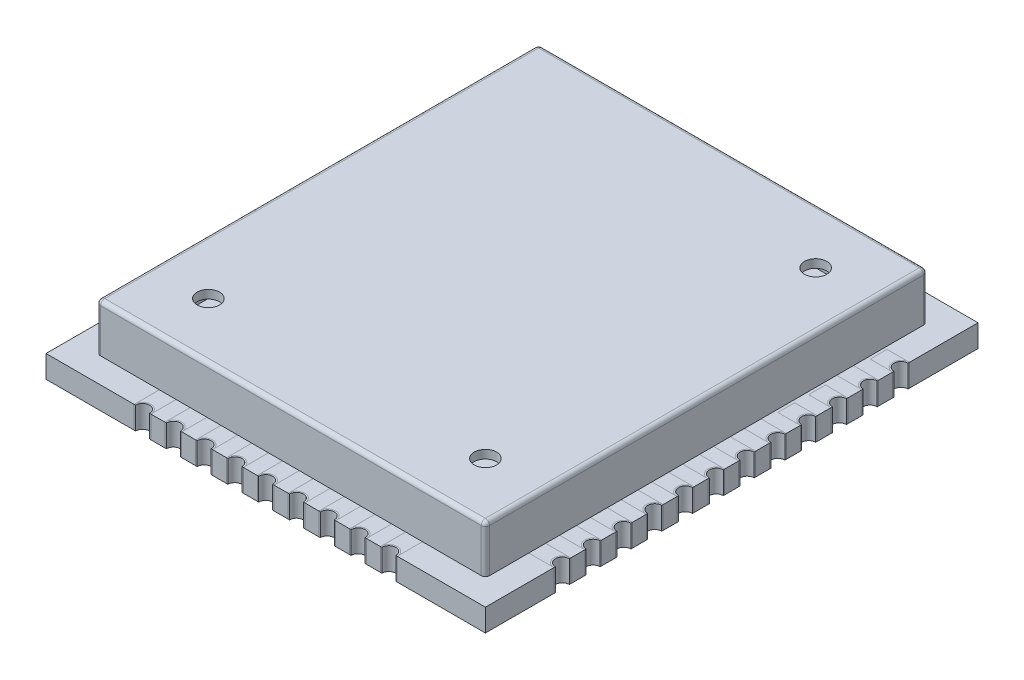
SolidWorks part; units mm, degrees
note: The reader was unsure of these and kept them because the rebuilt part matched: shared geometry of "Sketch5<2>", "Sketch5<3>", "Sketch5<4>", "Sketch3<2>".
other "Shield"
other "PCB"
ref_plane "Front Plane" through (0, 0, 0) normal (0, 0, 1) x (1, 0, 0)
ref_plane "Top Plane" through (0, 0, 0) normal (0, 1, 0) x (1, 0, 0)
ref_plane "Right Plane" through (0, 0, 0) normal (1, 0, 0) x (0, 0, -1)
sketch "Sketch1" plane through (0, 0, 0) normal (0, 1, 0) x (1, 0, 0)
  line L1 (-7.85, -8.8) -> (7.85, -8.8)
  line L2 (-7.85, -8.8) -> (-7.85, 8.8)
  line L3 (-7.85, 8.8) -> (7.85, 8.8)
  line L4 (7.85, -8.8) -> (7.85, 8.8)
  line L5 (-7.85, -8.8) -> (7.85, 8.8) construction
  line L6 (-7.85, 8.8) -> (7.85, -8.8) construction
  point P0 (0, 0)
  dimension "D1" = 17.6
  dimension "D2" = 15.7
extrude "PCB BASE" add sketch "Sketch1" along normal blind 0.8
sketch "Sketch2" plane through (0, 0, 0) normal (0, 1, 0) x (1, 0, 0)
  line L1 (-6.95, -7.9) -> (6.95, -7.9)
  line L2 (-6.95, -7.9) -> (-6.95, 7.9)
  line L3 (-6.95, 7.9) -> (6.95, 7.9)
  line L4 (6.95, -7.9) -> (6.95, 7.9)
  line L5 (-6.95, -7.9) -> (6.95, 7.9) construction
  line L6 (-6.95, 7.9) -> (6.95, -7.9) construction
  point P0 (0, 0)
  dimension "D1" = 15.8
  dimension "D2" = 13.9
extrude "SHIELD" add sketch "Sketch2" along normal blind 1.7 from surface at 0.8 separate body starting at face at (0, 0.8, 0)
shell "Shield shelling" thickness 0.3
sketch "Sketch4" plane through (0, 0, 0) normal (0, 1, 0) x (1, 0, 0)
  line L0 (-6.95, 7.9) -> (-6.95, -7.9) construction
  line L1 (-6.95, -7.9) -> (6.95, -7.9) construction
  line L2 (6.95, -7.9) -> (6.95, 7.9) construction
  line L3 (6.95, 7.9) -> (-6.95, 7.9) construction
  circle A0 centre (-4.95, -5.9) radius 0.4
  circle A1 centre (4.95, 5.9) radius 0.4
  circle A2 centre (4.95, -5.9) radius 0.4
  dimension "D1" = 0.8
  dimension "D2" = 0.8
  dimension "D3" = 0.8
  dimension "D4" = 2
  dimension "D5" = 2
  dimension "D6" = 2
  dimension "D7" = 2
extrude "Holes in shield" cut sketch "Sketch4" against normal up to next from surface
sketch "Sketch3" plane through (0, 0, 0) normal (0, 1, 0) x (1, 0, 0)
  line L0 (-7.85, 8.8) -> (-7.85, -8.8) construction
  line L1 (-7.85, -8.8) -> (7.85, -8.8) construction
  line L2 (-7.85, -5.75) -> (-7.85, -6.35)
  line L3 (-7.85, -4.65) -> (-7.85, -5.25)
  line L4 (-7.85, -3.55) -> (-7.85, -4.15)
  line L5 (-7.85, -2.45) -> (-7.85, -3.05)
  line L6 (-7.85, -1.35) -> (-7.85, -1.95)
  line L7 (-7.85, -0.25) -> (-7.85, -0.85)
  line L8 (-7.85, 0.85) -> (-7.85, 0.25)
  line L9 (-7.85, 1.95) -> (-7.85, 1.35)
  line L10 (-7.85, 3.05) -> (-7.85, 2.45)
  line L11 (-7.85, 4.15) -> (-7.85, 3.55)
  line L12 (-7.85, 5.25) -> (-7.85, 4.65)
  line L13 (-7.85, 6.35) -> (-7.85, 5.75)
  line L14 (0, 8.8) -> (0, -8.8) construction
  line L15 (7.85, 8.8) -> (-7.85, 8.8) construction
  line L16 (7.85, 6.35) -> (7.85, 5.75)
  line L17 (7.85, 5.25) -> (7.85, 4.65)
  line L18 (7.85, 4.15) -> (7.85, 3.55)
  line L19 (7.85, 3.05) -> (7.85, 2.45)
  line L20 (7.85, 1.95) -> (7.85, 1.35)
  line L21 (7.85, 0.85) -> (7.85, 0.25)
  line L22 (7.85, -0.25) -> (7.85, -0.85)
  line L23 (7.85, -1.35) -> (7.85, -1.95)
  line L24 (7.85, -2.45) -> (7.85, -3.05)
  line L25 (7.85, -3.55) -> (7.85, -4.15)
  line L26 (7.85, -4.65) -> (7.85, -5.25)
  line L27 (7.85, -5.75) -> (7.85, -6.35)
  line L28 (-4.7, -8.8) -> (-4.1, -8.8)
  line L29 (-3.6, -8.8) -> (-3, -8.8)
  line L30 (-2.5, -8.8) -> (-1.9, -8.8)
  line L31 (-1.4, -8.8) -> (-0.8, -8.8)
  line L32 (-0.3, -8.8) -> (0.3, -8.8)
  line L33 (0.8, -8.8) -> (1.4, -8.8)
  line L34 (1.9, -8.8) -> (2.5, -8.8)
  line L35 (3, -8.8) -> (3.6, -8.8)
  line L36 (4.1, -8.8) -> (4.7, -8.8)
  line L37 (-7.85, 0) -> (7.85, 0) construction
  line L38 (7.85, -8.8) -> (7.85, 8.8) construction
  line L39 (4.1, 8.8) -> (4.7, 8.8)
  line L40 (3, 8.8) -> (3.6, 8.8)
  line L41 (1.9, 8.8) -> (2.5, 8.8)
  line L42 (0.8, 8.8) -> (1.4, 8.8)
  line L43 (-0.3, 8.8) -> (0.3, 8.8)
  line L44 (-1.4, 8.8) -> (-0.8, 8.8)
  line L45 (-2.5, 8.8) -> (-1.9, 8.8)
  line L46 (-3.6, 8.8) -> (-3, 8.8)
  line L47 (-4.7, 8.8) -> (-4.1, 8.8)
  arc A0 (-7.85, -5.75) -> (-7.85, -6.35) centre (-7.85, -6.05) cw
  arc A1 (-7.85, -4.65) -> (-7.85, -5.25) centre (-7.85, -4.95) cw
  arc A2 (-7.85, -3.55) -> (-7.85, -4.15) centre (-7.85, -3.85) cw
  arc A3 (-7.85, -2.45) -> (-7.85, -3.05) centre (-7.85, -2.75) cw
  arc A4 (-7.85, -1.35) -> (-7.85, -1.95) centre (-7.85, -1.65) cw
  arc A5 (-7.85, -0.25) -> (-7.85, -0.85) centre (-7.85, -0.55) cw
  arc A6 (-7.85, 0.85) -> (-7.85, 0.25) centre (-7.85, 0.55) cw
  arc A7 (-7.85, 1.95) -> (-7.85, 1.35) centre (-7.85, 1.65) cw
  arc A8 (-7.85, 3.05) -> (-7.85, 2.45) centre (-7.85, 2.75) cw
  arc A9 (-7.85, 4.15) -> (-7.85, 3.55) centre (-7.85, 3.85) cw
  arc A10 (-7.85, 5.25) -> (-7.85, 4.65) centre (-7.85, 4.95) cw
  arc A11 (-7.85, 6.35) -> (-7.85, 5.75) centre (-7.85, 6.05) cw
  arc A12 (7.85, 6.35) -> (7.85, 5.75) centre (7.85, 6.05) ccw
  arc A13 (7.85, 5.25) -> (7.85, 4.65) centre (7.85, 4.95) ccw
  arc A14 (7.85, 4.15) -> (7.85, 3.55) centre (7.85, 3.85) ccw
  arc A15 (7.85, 3.05) -> (7.85, 2.45) centre (7.85, 2.75) ccw
  arc A16 (7.85, 1.95) -> (7.85, 1.35) centre (7.85, 1.65) ccw
  arc A17 (7.85, 0.85) -> (7.85, 0.25) centre (7.85, 0.55) ccw
  arc A18 (7.85, -0.25) -> (7.85, -0.85) centre (7.85, -0.55) ccw
  arc A19 (7.85, -1.35) -> (7.85, -1.95) centre (7.85, -1.65) ccw
  arc A20 (7.85, -2.45) -> (7.85, -3.05) centre (7.85, -2.75) ccw
  arc A21 (7.85, -3.55) -> (7.85, -4.15) centre (7.85, -3.85) ccw
  arc A22 (7.85, -4.65) -> (7.85, -5.25) centre (7.85, -4.95) ccw
  arc A23 (7.85, -5.75) -> (7.85, -6.35) centre (7.85, -6.05) ccw
  arc A24 (-4.7, -8.8) -> (-4.1, -8.8) centre (-4.4, -8.8) cw
  arc A25 (-3.6, -8.8) -> (-3, -8.8) centre (-3.3, -8.8) cw
  arc A26 (-2.5, -8.8) -> (-1.9, -8.8) centre (-2.2, -8.8) cw
  arc A27 (-1.4, -8.8) -> (-0.8, -8.8) centre (-1.1, -8.8) cw
  arc A28 (-0.3, -8.8) -> (0.3, -8.8) centre (0, -8.8) cw
  arc A29 (0.8, -8.8) -> (1.4, -8.8) centre (1.1, -8.8) cw
  arc A30 (1.9, -8.8) -> (2.5, -8.8) centre (2.2, -8.8) cw
  arc A31 (3, -8.8) -> (3.6, -8.8) centre (3.3, -8.8) cw
  arc A32 (4.1, -8.8) -> (4.7, -8.8) centre (4.4, -8.8) cw
  arc A33 (4.1, 8.8) -> (4.7, 8.8) centre (4.4, 8.8) ccw
  arc A34 (3, 8.8) -> (3.6, 8.8) centre (3.3, 8.8) ccw
  arc A35 (1.9, 8.8) -> (2.5, 8.8) centre (2.2, 8.8) ccw
  arc A36 (0.8, 8.8) -> (1.4, 8.8) centre (1.1, 8.8) ccw
  arc A37 (-0.3, 8.8) -> (0.3, 8.8) centre (0, 8.8) ccw
  arc A38 (-1.4, 8.8) -> (-0.8, 8.8) centre (-1.1, 8.8) ccw
  arc A39 (-2.5, 8.8) -> (-1.9, 8.8) centre (-2.2, 8.8) ccw
  arc A40 (-3.6, 8.8) -> (-3, 8.8) centre (-3.3, 8.8) ccw
  arc A41 (-4.7, 8.8) -> (-4.1, 8.8) centre (-4.4, 8.8) ccw
  point P0 (-7.85, -6.05)
  dimension "D2" = 0.3
  dimension "D4" = 0.3
  dimension "D1" = 2.75
  dimension "D5" = 3.45
  dimension "D3" = 12
  dimension "D6" = 9
extrude "Cut-Extrude1" cut sketch "Sketch3" against normal through all and the other way through all
sketch "Sketch5" plane through (0, 0, 0) normal (0, 1, 0) x (1, 0, 0)
  line L0 (-7.85, -4.65) -> (-6.85, -4.65)
  line L1 (-7.85, -5.75) -> (-6.85, -5.75)
  line L2 (-7.85, -5.75) -> (-7.85, -6.35)
  line L3 (-7.85, -6.35) -> (-6.85, -6.35)
  line L4 (-6.85, -5.75) -> (-6.85, -6.35)
  line L5 (-7.85, -4.65) -> (-7.85, -5.25)
  line L6 (-7.85, -5.25) -> (-6.85, -5.25)
  line L7 (-6.85, -4.65) -> (-6.85, -5.25)
  line L8 (-7.85, -3.55) -> (-6.85, -3.55)
  line L9 (-7.85, -3.55) -> (-7.85, -4.15)
  line L10 (-7.85, -4.15) -> (-6.85, -4.15)
  line L11 (-6.85, -3.55) -> (-6.85, -4.15)
  line L12 (-7.85, -2.45) -> (-6.85, -2.45)
  line L13 (-7.85, -2.45) -> (-7.85, -3.05)
  line L14 (-7.85, -3.05) -> (-6.85, -3.05)
  line L15 (-6.85, -2.45) -> (-6.85, -3.05)
  line L16 (-7.85, -1.35) -> (-6.85, -1.35)
  line L17 (-7.85, -1.35) -> (-7.85, -1.95)
  line L18 (-7.85, -1.95) -> (-6.85, -1.95)
  line L19 (-6.85, -1.35) -> (-6.85, -1.95)
  line L20 (-7.85, -0.25) -> (-6.85, -0.25)
  line L21 (-7.85, -0.25) -> (-7.85, -0.85)
  line L22 (-7.85, -0.85) -> (-6.85, -0.85)
  line L23 (-6.85, -0.25) -> (-6.85, -0.85)
  line L24 (-7.85, 0.85) -> (-6.85, 0.85)
  line L25 (-7.85, 0.85) -> (-7.85, 0.25)
  line L26 (-7.85, 0.25) -> (-6.85, 0.25)
  line L27 (-6.85, 0.85) -> (-6.85, 0.25)
  line L28 (-7.85, 1.95) -> (-6.85, 1.95)
  line L29 (-7.85, 1.95) -> (-7.85, 1.35)
  line L30 (-7.85, 1.35) -> (-6.85, 1.35)
  line L31 (-6.85, 1.95) -> (-6.85, 1.35)
  line L32 (-7.85, 3.05) -> (-6.85, 3.05)
  line L33 (-7.85, 3.05) -> (-7.85, 2.45)
  line L34 (-7.85, 2.45) -> (-6.85, 2.45)
  line L35 (-6.85, 3.05) -> (-6.85, 2.45)
  line L36 (-7.85, 4.15) -> (-6.85, 4.15)
  line L37 (-7.85, 4.15) -> (-7.85, 3.55)
  line L38 (-7.85, 3.55) -> (-6.85, 3.55)
  line L39 (-6.85, 4.15) -> (-6.85, 3.55)
  line L40 (-7.85, 5.25) -> (-6.85, 5.25)
  line L41 (-7.85, 5.25) -> (-7.85, 4.65)
  line L42 (-7.85, 4.65) -> (-6.85, 4.65)
  line L43 (-6.85, 5.25) -> (-6.85, 4.65)
  line L44 (-7.85, 6.35) -> (-6.85, 6.35)
  line L45 (-7.85, 6.35) -> (-7.85, 5.75)
  line L46 (-7.85, 5.75) -> (-6.85, 5.75)
  line L47 (-6.85, 6.35) -> (-6.85, 5.75)
  line L48 (-7.85, 0) -> (7.85, 0) construction
  line L49 (-7.85, 0.25) -> (-7.85, -0.25) construction
  line L50 (7.85, -0.25) -> (7.85, 0.25) construction
  line L51 (0, 8.5) -> (0, -8.5) construction
  line L52 (7.85, 5.25) -> (7.05, 5.25) [skipped]
  line L53 (7.85, 6.35) -> (7.05, 6.35)
  line L54 (7.85, 6.35) -> (7.85, 5.75)
  line L55 (7.85, 5.75) -> (7.05, 5.75)
  line L56 (7.05, 6.35) -> (7.05, 5.75)
  line L57 (7.85, 5.25) -> (7.85, 4.65) [skipped]
  line L58 (7.85, 4.65) -> (7.05, 4.65) [skipped]
  line L59 (7.05, 5.25) -> (7.05, 4.65) [skipped]
  line L60 (7.85, 4.15) -> (7.05, 4.15)
  line L61 (7.85, 4.15) -> (7.85, 3.55)
  line L62 (7.85, 3.55) -> (7.05, 3.55)
  line L63 (7.05, 4.15) -> (7.05, 3.55)
  line L64 (7.85, 3.05) -> (7.05, 3.05)
  line L65 (7.85, 3.05) -> (7.85, 2.45)
  line L66 (7.85, 2.45) -> (7.05, 2.45)
  line L67 (7.05, 3.05) -> (7.05, 2.45)
  line L68 (6.85, 1.95) -> (6.85, 1.35)
  line L69 (7.85, 1.35) -> (6.85, 1.35)
  line L70 (7.85, 1.95) -> (7.85, 1.35)
  line L71 (7.85, 1.95) -> (6.85, 1.95)
  line L72 (6.85, 0.85) -> (6.85, 0.25)
  line L73 (7.85, 0.25) -> (6.85, 0.25)
  line L74 (7.85, 0.85) -> (7.85, 0.25)
  line L75 (7.85, 0.85) -> (6.85, 0.85)
  line L76 (6.85, -0.25) -> (6.85, -0.85)
  line L77 (7.85, -0.85) -> (6.85, -0.85)
  line L78 (7.85, -0.25) -> (7.85, -0.85)
  line L79 (7.85, -0.25) -> (6.85, -0.25)
  line L80 (6.85, -1.35) -> (6.85, -1.95)
  line L81 (7.85, -1.95) -> (6.85, -1.95)
  line L82 (7.85, -1.35) -> (7.85, -1.95)
  line L83 (7.85, -1.35) -> (6.85, -1.35)
  line L84 (6.85, -2.45) -> (6.85, -3.05)
  line L85 (7.85, -3.05) -> (6.85, -3.05)
  line L86 (7.85, -2.45) -> (7.85, -3.05)
  line L87 (7.85, -2.45) -> (6.85, -2.45)
  line L88 (6.85, -3.55) -> (6.85, -4.15)
  line L89 (7.85, -4.15) -> (6.85, -4.15)
  line L90 (7.85, -3.55) -> (7.85, -4.15)
  line L91 (7.85, -3.55) -> (6.85, -3.55)
  line L92 (6.85, -4.65) -> (6.85, -5.25)
  line L93 (7.85, -5.25) -> (6.85, -5.25)
  line L94 (7.85, -4.65) -> (7.85, -5.25)
  line L95 (6.85, -5.75) -> (6.85, -6.35)
  line L96 (7.85, -6.35) -> (6.85, -6.35)
  line L97 (7.85, -5.75) -> (7.85, -6.35)
  line L98 (7.85, -5.75) -> (6.85, -5.75)
  line L99 (7.85, -4.65) -> (6.85, -4.65)
  line L100 (-3.6, -8.8) -> (-3, -8.8)
  line L101 (-4.7, -8.8) -> (-4.1, -8.8)
  line L102 (-4.7, -8.8) -> (-4.7, -7.8)
  line L103 (-4.7, -7.8) -> (-4.1, -7.8)
  line L104 (-4.1, -8.8) -> (-4.1, -7.8)
  line L105 (-3.6, -8.8) -> (-3.6, -7.8)
  line L106 (-3.6, -7.8) -> (-3, -7.8)
  line L107 (-3, -8.8) -> (-3, -7.8)
  line L108 (-2.5, -8.8) -> (-1.9, -8.8)
  line L109 (-2.5, -8.8) -> (-2.5, -7.8)
  line L110 (-2.5, -7.8) -> (-1.9, -7.8)
  line L111 (-1.9, -8.8) -> (-1.9, -7.8)
  line L112 (-1.4, -8.8) -> (-0.8, -8.8)
  line L113 (-1.4, -8.8) -> (-1.4, -7.8)
  line L114 (-1.4, -7.8) -> (-0.8, -7.8)
  line L115 (-0.8, -8.8) -> (-0.8, -7.8)
  line L116 (-0.3, -8.8) -> (0.3, -8.8)
  line L117 (-0.3, -8.8) -> (-0.3, -7.8)
  line L118 (-0.3, -7.8) -> (0.3, -7.8)
  line L119 (0.3, -8.8) -> (0.3, -7.8)
  line L120 (0.8, -8.8) -> (1.4, -8.8)
  line L121 (0.8, -8.8) -> (0.8, -7.8)
  line L122 (0.8, -7.8) -> (1.4, -7.8)
  line L123 (1.4, -8.8) -> (1.4, -7.8)
  line L124 (1.9, -8.8) -> (2.5, -8.8)
  line L125 (1.9, -8.8) -> (1.9, -7.8)
  line L126 (1.9, -7.8) -> (2.5, -7.8)
  line L127 (2.5, -8.8) -> (2.5, -7.8)
  line L128 (3, -8.8) -> (3.6, -8.8)
  line L129 (3, -8.8) -> (3, -7.8)
  line L130 (3, -7.8) -> (3.6, -7.8)
  line L131 (3.6, -8.8) -> (3.6, -7.8)
  line L132 (4.1, -8.8) -> (4.7, -8.8)
  line L133 (4.1, -8.8) -> (4.1, -7.8)
  line L134 (4.1, -7.8) -> (4.7, -7.8)
  line L135 (4.7, -8.8) -> (4.7, -7.8)
  line L136 (4.7, 8.8) -> (4.7, 7.8)
  line L137 (4.1, 7.8) -> (4.7, 7.8)
  line L138 (4.1, 8.8) -> (4.1, 7.8)
  line L139 (4.1, 8.8) -> (4.7, 8.8)
  line L140 (3.6, 8.8) -> (3.6, 7.8)
  line L141 (3, 7.8) -> (3.6, 7.8)
  line L142 (3, 8.8) -> (3, 7.8)
  line L143 (3, 8.8) -> (3.6, 8.8)
  line L144 (2.5, 8.8) -> (2.5, 7.8)
  line L145 (1.9, 7.8) -> (2.5, 7.8)
  line L146 (1.9, 8.8) -> (1.9, 7.8)
  line L147 (1.9, 8.8) -> (2.5, 8.8)
  line L148 (1.4, 8.8) -> (1.4, 7.8)
  line L149 (0.8, 7.8) -> (1.4, 7.8)
  line L150 (0.8, 8.8) -> (0.8, 7.8)
  line L151 (0.8, 8.8) -> (1.4, 8.8)
  line L152 (0.3, 8.8) -> (0.3, 7.8)
  line L153 (-0.3, 7.8) -> (0.3, 7.8)
  line L154 (-0.3, 8.8) -> (-0.3, 7.8)
  line L155 (-0.3, 8.8) -> (0.3, 8.8)
  line L156 (-0.8, 8.8) -> (-0.8, 7.8)
  line L157 (-1.4, 7.8) -> (-0.8, 7.8)
  line L158 (-1.4, 8.8) -> (-1.4, 7.8)
  line L159 (-1.4, 8.8) -> (-0.8, 8.8)
  line L160 (-1.9, 8.8) -> (-1.9, 7.8)
  line L161 (-2.5, 7.8) -> (-1.9, 7.8)
  line L162 (-2.5, 8.8) -> (-2.5, 7.8)
  line L163 (-2.5, 8.8) -> (-1.9, 8.8)
  line L164 (-3, 8.8) -> (-3, 7.8)
  line L165 (-3.6, 7.8) -> (-3, 7.8)
  line L166 (-3.6, 8.8) -> (-3.6, 7.8)
  line L167 (-4.1, 8.8) -> (-4.1, 7.8)
  line L168 (-4.7, 7.8) -> (-4.1, 7.8)
  line L169 (-4.7, 8.8) -> (-4.7, 7.8)
  line L170 (-4.7, 8.8) -> (-4.1, 8.8)
  line L171 (-3.6, 8.8) -> (-3, 8.8)
  line L172 (-4.15, 3.9) -> (-3.15, 4.9)
  line L173 (3.8, -5.8) -> (4.6, -5.8)
  line L174 (3.8, -5.8) -> (3.8, -6.8)
  line L175 (3.8, -6.8) -> (4.6, -6.8)
  line L176 (4.6, -5.8) -> (4.6, -6.8)
  line L177 (3.8, -5.8) -> (4.6, -6.8) construction
  line L178 (3.8, -6.8) -> (4.6, -5.8) construction
  line L180 (7.85, -8.8) -> (7.85, -6.35) construction
  line L181 (4.7, -8.8) -> (7.85, -8.8) construction
  line L182 (2.4, -5.8) -> (2.4, -6.8)
  line L183 (2.4, -5.8) -> (3.2, -5.8)
  line L184 (3.2, -5.8) -> (3.2, -6.8)
  line L185 (2.4, -6.8) -> (3.2, -6.8)
  line L186 (2.4, -6.8) -> (3.2, -5.8) construction
  line L187 (2.4, -5.8) -> (3.2, -6.8) construction
  line L188 (1, -5.8) -> (1, -6.8)
  line L189 (1, -5.8) -> (1.8, -5.8)
  line L190 (1.8, -5.8) -> (1.8, -6.8)
  line L191 (1, -6.8) -> (1.8, -6.8)
  line L192 (1, -6.8) -> (1.8, -5.8) construction
  line L193 (1, -5.8) -> (1.8, -6.8) construction
  line L194 (-0.4, -5.8) -> (-0.4, -6.8)
  line L195 (-0.4, -5.8) -> (0.4, -5.8)
  line L196 (0.4, -5.8) -> (0.4, -6.8)
  line L197 (-0.4, -6.8) -> (0.4, -6.8)
  line L198 (-0.4, -6.8) -> (0.4, -5.8) construction
  line L199 (-0.4, -5.8) -> (0.4, -6.8) construction
  line L200 (-1.8, -5.8) -> (-1.8, -6.8)
  line L201 (-1.8, -5.8) -> (-1, -5.8)
  line L202 (-1, -5.8) -> (-1, -6.8)
  line L203 (-1.8, -6.8) -> (-1, -6.8)
  line L204 (-1.8, -6.8) -> (-1, -5.8) construction
  line L205 (-1.8, -5.8) -> (-1, -6.8) construction
  line L206 (-3.2, -5.8) -> (-3.2, -6.8)
  line L207 (-3.2, -5.8) -> (-2.4, -5.8)
  line L208 (-2.4, -5.8) -> (-2.4, -6.8)
  line L209 (-3.2, -6.8) -> (-2.4, -6.8)
  line L210 (-3.2, -6.8) -> (-2.4, -5.8) construction
  line L211 (-3.2, -5.8) -> (-2.4, -6.8) construction
  line L212 (-4.6, -5.8) -> (-4.6, -6.8)
  line L213 (-4.6, -5.8) -> (-3.8, -5.8)
  line L214 (-3.8, -5.8) -> (-3.8, -6.8)
  line L215 (-4.6, -6.8) -> (-3.8, -6.8)
  line L216 (-4.6, -6.8) -> (-3.8, -5.8) construction
  line L217 (-4.6, -5.8) -> (-3.8, -6.8) construction
  line L218 (-4.6, 5.8) -> (-3.8, 6.8) construction
  line L219 (-4.6, 6.8) -> (-3.8, 5.8) construction
  line L220 (-4.6, 6.8) -> (-3.8, 6.8)
  line L221 (-3.8, 5.8) -> (-3.8, 6.8)
  line L222 (-4.6, 5.8) -> (-3.8, 5.8)
  line L223 (-4.6, 5.8) -> (-4.6, 6.8)
  line L224 (-3.2, 6.8) -> (-2.4, 6.8)
  line L225 (-2.4, 5.8) -> (-2.4, 6.8)
  line L226 (-3.2, 5.8) -> (-2.4, 5.8)
  line L227 (-3.2, 5.8) -> (-3.2, 6.8)
  line L228 (-3.2, 5.8) -> (-2.4, 6.8) construction
  line L229 (-3.2, 6.8) -> (-2.4, 5.8) construction
  line L230 (-1.8, 6.8) -> (-1, 6.8)
  line L231 (-1, 5.8) -> (-1, 6.8)
  line L232 (-1.8, 5.8) -> (-1, 5.8)
  line L233 (-1.8, 5.8) -> (-1.8, 6.8)
  line L234 (-1.8, 5.8) -> (-1, 6.8) construction
  line L235 (-1.8, 6.8) -> (-1, 5.8) construction
  line L236 (-0.4, 6.8) -> (0.4, 6.8)
  line L237 (0.4, 5.8) -> (0.4, 6.8)
  line L238 (-0.4, 5.8) -> (0.4, 5.8)
  line L239 (-0.4, 5.8) -> (-0.4, 6.8)
  line L240 (-0.4, 5.8) -> (0.4, 6.8) construction
  line L241 (-0.4, 6.8) -> (0.4, 5.8) construction
  line L242 (1, 6.8) -> (1.8, 6.8)
  line L243 (1.8, 5.8) -> (1.8, 6.8)
  line L244 (1, 5.8) -> (1.8, 5.8)
  line L245 (1, 5.8) -> (1, 6.8)
  line L246 (1, 5.8) -> (1.8, 6.8) construction
  line L247 (1, 6.8) -> (1.8, 5.8) construction
  line L248 (2.4, 6.8) -> (3.2, 6.8)
  line L249 (3.2, 5.8) -> (3.2, 6.8)
  line L250 (2.4, 5.8) -> (3.2, 5.8)
  line L251 (2.4, 5.8) -> (2.4, 6.8)
  line L252 (2.4, 5.8) -> (3.2, 6.8) construction
  line L253 (2.4, 6.8) -> (3.2, 5.8) construction
  line L254 (4.85, -3.1) -> (5.85, -3.1)
  line L255 (4.85, -5.3) -> (5.85, -5.3)
  line L256 (4.85, -5.3) -> (4.85, -4.5)
  line L257 (4.85, -4.5) -> (5.85, -4.5)
  line L258 (5.85, -5.3) -> (5.85, -4.5)
  line L259 (4.85, -5.3) -> (5.85, -4.5) construction
  line L260 (4.85, -4.5) -> (5.85, -5.3) construction
  line L261 (4.85, -3.9) -> (4.85, -3.1)
  line L262 (4.85, -3.9) -> (5.85, -3.9)
  line L263 (5.85, -3.9) -> (5.85, -3.1)
  line L264 (4.85, -3.9) -> (5.85, -3.1) construction
  line L265 (4.85, -3.1) -> (5.85, -3.9) construction
  line L266 (4.85, -1.7) -> (5.85, -1.7)
  line L267 (4.85, -2.5) -> (4.85, -1.7)
  line L268 (4.85, -2.5) -> (5.85, -2.5)
  line L269 (5.85, -2.5) -> (5.85, -1.7)
  line L270 (4.85, -2.5) -> (5.85, -1.7) construction
  line L271 (4.85, -1.7) -> (5.85, -2.5) construction
  line L272 (4.85, -0.3) -> (5.85, -0.3)
  line L273 (4.85, -1.1) -> (4.85, -0.3)
  line L274 (4.85, -1.1) -> (5.85, -1.1)
  line L275 (5.85, -1.1) -> (5.85, -0.3)
  line L276 (4.85, -1.1) -> (5.85, -0.3) construction
  line L277 (4.85, -0.3) -> (5.85, -1.1) construction
  line L278 (4.85, 1.1) -> (5.85, 1.1)
  line L279 (4.85, 0.3) -> (4.85, 1.1)
  line L280 (4.85, 0.3) -> (5.85, 0.3)
  line L281 (5.85, 0.3) -> (5.85, 1.1)
  line L282 (4.85, 0.3) -> (5.85, 1.1) construction
  line L283 (4.85, 1.1) -> (5.85, 0.3) construction
  line L284 (-4.85, -4.5) -> (-5.85, -5.3) construction
  line L285 (-4.85, -5.3) -> (-5.85, -4.5) construction
  line L286 (-5.85, -5.3) -> (-5.85, -4.5)
  line L287 (-4.85, -5.3) -> (-5.85, -5.3)
  line L288 (-4.85, -5.3) -> (-4.85, -4.5)
  line L289 (-4.85, -4.5) -> (-5.85, -4.5)
  line L290 (-5.85, -3.9) -> (-5.85, -3.1)
  line L291 (-4.85, -3.9) -> (-5.85, -3.9)
  line L292 (-4.85, -3.9) -> (-4.85, -3.1)
  line L293 (-4.85, -3.1) -> (-5.85, -3.1)
  line L294 (-4.85, -3.1) -> (-5.85, -3.9) construction
  line L295 (-4.85, -3.9) -> (-5.85, -3.1) construction
  line L296 (-5.85, -2.5) -> (-5.85, -1.7)
  line L297 (-4.85, -2.5) -> (-5.85, -2.5)
  line L298 (-4.85, -2.5) -> (-4.85, -1.7)
  line L299 (-4.85, -1.7) -> (-5.85, -1.7)
  line L300 (-4.85, -1.7) -> (-5.85, -2.5) construction
  line L301 (-4.85, -2.5) -> (-5.85, -1.7) construction
  line L302 (-5.85, -1.1) -> (-5.85, -0.3)
  line L303 (-4.85, -1.1) -> (-5.85, -1.1)
  line L304 (-4.85, -1.1) -> (-4.85, -0.3)
  line L305 (-4.85, -0.3) -> (-5.85, -0.3)
  line L306 (-4.85, -0.3) -> (-5.85, -1.1) construction
  line L307 (-4.85, -1.1) -> (-5.85, -0.3) construction
  line L308 (-5.85, 0.3) -> (-5.85, 1.1)
  line L309 (-4.85, 0.3) -> (-5.85, 0.3)
  line L310 (-4.85, 0.3) -> (-4.85, 1.1)
  line L311 (-4.85, 1.1) -> (-5.85, 1.1)
  line L312 (-4.85, 1.1) -> (-5.85, 0.3) construction
  line L313 (-4.85, 0.3) -> (-5.85, 1.1) construction
  line L314 (-5.85, 1.7) -> (-5.85, 2.5)
  line L315 (-4.85, 1.7) -> (-5.85, 1.7)
  line L316 (-4.85, 1.7) -> (-4.85, 2.5)
  line L317 (-4.85, 2.5) -> (-5.85, 2.5)
  line L318 (-4.85, 2.5) -> (-5.85, 1.7) construction
  line L319 (-4.85, 1.7) -> (-5.85, 2.5) construction
  line L320 (-5.85, 3.1) -> (-5.85, 3.9)
  line L321 (-4.85, 3.1) -> (-5.85, 3.1)
  line L322 (-4.85, 3.1) -> (-4.85, 3.9)
  line L323 (-4.85, 3.9) -> (-5.85, 3.9)
  line L324 (-4.85, 3.9) -> (-5.85, 3.1) construction
  line L325 (-4.85, 3.1) -> (-5.85, 3.9) construction
  line L326 (-5.85, 4.5) -> (-5.85, 5.3)
  line L327 (-4.85, 4.5) -> (-5.85, 4.5)
  line L328 (-4.85, 4.5) -> (-4.85, 5.3)
  line L329 (-4.85, 5.3) -> (-5.85, 5.3)
  line L330 (-4.85, 5.3) -> (-5.85, 4.5) construction
  line L331 (-4.85, 4.5) -> (-5.85, 5.3) construction
  line L332 (-1.25, -4.9) -> (-1.25, -1.9)
  line L333 (4.15, -4.9) -> (1.65, -4.9)
  line L334 (4.15, -4.9) -> (4.15, -1.9)
  line L335 (4.15, -1.9) -> (1.65, -1.9)
  line L336 (1.65, -4.9) -> (1.65, -1.9)
  line L337 (4.15, -4.9) -> (1.65, -1.9) construction
  line L338 (4.15, -1.9) -> (1.65, -4.9) construction
  line L339 (1.25, -1.9) -> (-1.25, -1.9)
  line L340 (1.25, -4.9) -> (1.25, -1.9)
  line L341 (1.25, -4.9) -> (-1.25, -4.9)
  line L342 (1.25, -1.9) -> (-1.25, -4.9) construction
  line L343 (1.25, -4.9) -> (-1.25, -1.9) construction
  line L344 (-4.15, -4.9) -> (-4.15, -1.9)
  line L345 (-1.65, -1.9) -> (-4.15, -1.9)
  line L346 (-1.65, -4.9) -> (-1.65, -1.9)
  line L347 (-1.65, -4.9) -> (-4.15, -4.9)
  line L348 (-1.65, -1.9) -> (-4.15, -4.9) construction
  line L349 (-1.65, -4.9) -> (-4.15, -1.9) construction
  line L350 (-1.25, -1.5) -> (-1.25, 1.5)
  line L351 (1.25, 1.5) -> (-1.25, 1.5)
  line L352 (1.25, -1.5) -> (1.25, 1.5)
  line L353 (1.25, -1.5) -> (-1.25, -1.5)
  line L354 (1.25, 1.5) -> (-1.25, -1.5) construction
  line L355 (1.25, -1.5) -> (-1.25, 1.5) construction
  line L356 (-4.15, -1.5) -> (-4.15, 1.5)
  line L357 (-1.65, 1.5) -> (-4.15, 1.5)
  line L358 (-1.65, -1.5) -> (-1.65, 1.5)
  line L359 (-1.65, -1.5) -> (-4.15, -1.5)
  line L360 (-1.65, 1.5) -> (-4.15, -1.5) construction
  line L361 (-1.65, -1.5) -> (-4.15, 1.5) construction
  line L362 (-1.25, 1.9) -> (-1.25, 4.9)
  line L363 (1.25, 4.9) -> (-1.25, 4.9)
  line L364 (1.25, 1.9) -> (1.25, 4.9)
  line L365 (1.25, 1.9) -> (-1.25, 1.9)
  line L366 (1.25, 4.9) -> (-1.25, 1.9) construction
  line L367 (1.25, 1.9) -> (-1.25, 4.9) construction
  line L368 (-4.15, 1.9) -> (-4.15, 3.9)
  line L369 (-1.65, 4.9) -> (-3.15, 4.9)
  line L370 (-1.65, 1.9) -> (-1.65, 4.9)
  line L371 (-1.65, 1.9) -> (-4.15, 1.9)
  line L372 (-1.65, 4.9) -> (-4.15, 1.9) construction
  line L373 (-1.65, 1.9) -> (-3.6955, 4.3545) construction
  line L374 (1.65, -1.5) -> (1.65, 1.5)
  line L375 (4.15, 1.5) -> (1.65, 1.5)
  line L376 (4.15, -1.5) -> (4.15, 1.5)
  line L377 (4.15, -1.5) -> (1.65, -1.5)
  line L378 (4.15, 1.5) -> (1.65, -1.5) construction
  line L379 (4.15, -1.5) -> (1.65, 1.5) construction
  line L380 (1.65, 1.9) -> (1.65, 4.9)
  line L381 (4.15, 4.9) -> (1.65, 4.9)
  line L382 (4.15, 1.9) -> (4.15, 4.9)
  line L383 (4.15, 1.9) -> (1.65, 1.9)
  line L384 (4.15, 4.9) -> (1.65, 1.9) construction
  line L385 (4.15, 1.9) -> (1.65, 4.9) construction
  line L387 (7.85, 5.25) -> (6.65, 5.25)
  line L388 (7.85, 5.25) -> (7.85, 4.65)
  line L389 (7.85, 4.65) -> (6.65, 4.65)
  line L390 (6.65, 5.25) -> (6.65, 4.65)
  line L391 (6.55, 7.1986) -> (6.55, 6.1986)
  line L392 (6.55, 3.6986) -> (6.55, 2.6986)
  arc A0 (-0.3, 8.8) -> (0.3, 8.8) centre (0, 8.8) ccw construction
  arc A1 (0.3, -8.8) -> (-0.3, -8.8) centre (0, -8.8) ccw construction
  arc A2 (6.55, 6.1986) -> (6.55, 3.6986) centre (6.55, 4.9486) ccw
  arc A3 (6.55, 2.6986) -> (6.55, 7.1986) centre (6.55, 4.9486) cw
  point P186 (4.2, -6.3)
  point P223 (5.35, -4.9)
  point P270 (2.9, -3.4)
  dimension "D25" = 1.25
  dimension "D26" = 2.25
  dimension "D1" = 1
  dimension "D3" = 1
  dimension "D5" = 3.65
  dimension "D6" = 1
  dimension "D7" = 0.8
  dimension "D8" = 2.5
  dimension "D11" = 1
  dimension "D12" = 0.8
  dimension "D13" = 2.5
  dimension "D14" = 3.9
  dimension "D17" = 5.4
  dimension "D18" = 4.95
  dimension "D19" = 3
  dimension "D20" = 2.5
  dimension "D23" = 1.5
  dimension "D24" = 2
  dimension "D27" = 0.8
  dimension "D29" = 1.2
  dimension "D30" = 0.5
  dimension "D2" = 12
  dimension "D4" = 9
  dimension "D9" = 7
  dimension "D10" = 6
  dimension "D15" = 5
  dimension "D16" = 8
  dimension "D21" = 3
  dimension "D22" = 3
  dimension "D28" = 4
extrude "Cut-Extrude5" cut sketch "Sketch5" along normal blind 0.05
extrude "Cut-Extrude7" cut sketch "Sketch5<2>" against normal blind 0.05 from offset 0.8
sketch "Sketch5<2>" plane through (0, 0, 0) normal (0, 1, 0) x (1, 0, 0) same geometry as "Sketch5"
extrude "Boss-Extrude3" add sketch "Sketch5<3>" along normal blind 0.05 separate body
sketch "Sketch5<3>" plane through (0, 0, 0) normal (0, 1, 0) x (1, 0, 0) same geometry as "Sketch5"
extrude "Boss-Extrude4" add sketch "Sketch5<4>" against normal blind 0.05 from offset 0.8 separate body
sketch "Sketch5<4>" plane through (0, 0, 0) normal (0, 1, 0) x (1, 0, 0) same geometry as "Sketch5"
extrude "Cut-Extrude8" cut sketch "Sketch3<2>" against normal through all and the other way through all
sketch "Sketch3<2>" plane through (0, 0, 0) normal (0, 1, 0) x (1, 0, 0) same geometry as "Sketch3"
sketch "Sketch6" plane through (0, 0, 0) normal (0, 1, 0) x (1, 0, 0)
  line L2 (-7.85, -5.75) -> (-7.85, -5.8)
  line L3 (-4.7, -8.8) -> (-4.65, -8.8)
  line L4 (-4.1, -8.8) -> (-4.15, -8.8)
  line L5 (-3.6, -8.8) -> (-3.55, -8.8)
  line L6 (-3, -8.8) -> (-3.05, -8.8)
  line L7 (-2.5, -8.8) -> (-2.45, -8.8)
  line L8 (-1.9, -8.8) -> (-1.95, -8.8)
  line L9 (-1.4, -8.8) -> (-1.35, -8.8)
  line L10 (-0.8, -8.8) -> (-0.85, -8.8)
  line L11 (-0.3, -8.8) -> (-0.25, -8.8)
  line L12 (0.3, -8.8) -> (0.25, -8.8)
  line L13 (0.8, -8.8) -> (0.85, -8.8)
  line L14 (0, 8.8) -> (0, -8.8) construction
  line L16 (7.85, -5.75) -> (7.85, -5.8)
  line L17 (7.85, -6.35) -> (7.85, -6.3)
  line L18 (7.85, -4.65) -> (7.85, -4.7)
  line L19 (7.85, -5.25) -> (7.85, -5.2)
  line L20 (7.85, -3.55) -> (7.85, -3.6)
  line L21 (7.85, -4.15) -> (7.85, -4.1)
  line L22 (7.85, -2.45) -> (7.85, -2.5)
  line L23 (7.85, -3.05) -> (7.85, -3)
  line L24 (7.85, -1.35) -> (7.85, -1.4)
  line L25 (7.85, -1.95) -> (7.85, -1.9)
  line L26 (7.85, -0.25) -> (7.85, -0.3)
  line L27 (7.85, -0.85) -> (7.85, -0.8)
  line L28 (1.4, -8.8) -> (1.35, -8.8)
  line L29 (1.9, -8.8) -> (1.95, -8.8)
  line L30 (2.5, -8.8) -> (2.45, -8.8)
  line L31 (3, -8.8) -> (3.05, -8.8)
  line L32 (3.6, -8.8) -> (3.55, -8.8)
  line L33 (4.1, -8.8) -> (4.15, -8.8)
  line L34 (4.7, -8.8) -> (4.65, -8.8)
  line L35 (7.85, 0.85) -> (7.85, 0.8)
  line L36 (7.85, 0.25) -> (7.85, 0.3)
  line L37 (-7.85, 0) -> (7.85, 0) construction
  line L39 (-4.7, 8.8) -> (-4.65, 8.8)
  line L40 (-4.1, 8.8) -> (-4.15, 8.8)
  line L41 (-3.6, 8.8) -> (-3.55, 8.8)
  line L42 (-3, 8.8) -> (-3.05, 8.8)
  line L43 (-2.5, 8.8) -> (-2.45, 8.8)
  line L44 (-1.9, 8.8) -> (-1.95, 8.8)
  line L45 (-1.4, 8.8) -> (-1.35, 8.8)
  line L46 (-0.8, 8.8) -> (-0.85, 8.8)
  line L47 (-0.3, 8.8) -> (-0.25, 8.8)
  line L48 (-7.85, -6.35) -> (-7.85, -6.3)
  line L49 (-7.85, -4.65) -> (-7.85, -4.7)
  line L50 (-7.85, -5.25) -> (-7.85, -5.2)
  line L51 (-7.85, -3.55) -> (-7.85, -3.6)
  line L52 (-7.85, -4.15) -> (-7.85, -4.1)
  line L53 (-7.85, -2.45) -> (-7.85, -2.5)
  line L54 (-7.85, -3.05) -> (-7.85, -3)
  line L55 (-7.85, -1.35) -> (-7.85, -1.4)
  line L56 (-7.85, -1.95) -> (-7.85, -1.9)
  line L57 (-7.85, -0.25) -> (-7.85, -0.3)
  line L58 (-7.85, -0.85) -> (-7.85, -0.8)
  line L59 (-7.85, 0.85) -> (-7.85, 0.8)
  line L60 (-7.85, 0.25) -> (-7.85, 0.3)
  line L61 (-7.85, 1.95) -> (-7.85, 1.9)
  line L62 (-7.85, 1.35) -> (-7.85, 1.4)
  line L63 (-7.85, 3.05) -> (-7.85, 3)
  line L64 (-7.85, 2.45) -> (-7.85, 2.5)
  line L65 (-7.85, 4.15) -> (-7.85, 4.1)
  line L66 (-7.85, 3.55) -> (-7.85, 3.6)
  line L67 (-7.85, 5.25) -> (-7.85, 5.2)
  line L68 (-7.85, 4.65) -> (-7.85, 4.7)
  line L69 (-7.85, 6.35) -> (-7.85, 6.3)
  line L70 (-7.85, 5.75) -> (-7.85, 5.8)
  line L71 (7.85, 1.95) -> (7.85, 1.9)
  line L72 (7.85, 1.35) -> (7.85, 1.4)
  line L73 (7.85, 3.05) -> (7.85, 3)
  line L74 (7.85, 2.45) -> (7.85, 2.5)
  line L75 (7.85, 4.15) -> (7.85, 4.1)
  line L76 (7.85, 3.55) -> (7.85, 3.6)
  line L77 (7.85, 5.25) -> (7.85, 5.2)
  line L78 (7.85, 4.65) -> (7.85, 4.7)
  line L79 (7.85, 6.35) -> (7.85, 6.3)
  line L80 (7.85, 5.75) -> (7.85, 5.8)
  line L81 (0.3, 8.8) -> (0.25, 8.8)
  line L82 (0.8, 8.8) -> (0.85, 8.8)
  line L83 (1.4, 8.8) -> (1.35, 8.8)
  line L84 (1.9, 8.8) -> (1.95, 8.8)
  line L85 (2.5, 8.8) -> (2.45, 8.8)
  line L86 (3, 8.8) -> (3.05, 8.8)
  line L87 (3.6, 8.8) -> (3.55, 8.8)
  line L88 (4.1, 8.8) -> (4.15, 8.8)
  line L89 (4.7, 8.8) -> (4.65, 8.8)
  arc A0 (-7.85, -5.75) -> (-7.85, -6.35) centre (-7.85, -6.05) cw
  arc A1 (-7.85, -4.65) -> (-7.85, -5.25) centre (-7.85, -4.95) cw
  arc A2 (-7.85, -3.55) -> (-7.85, -4.15) centre (-7.85, -3.85) cw
  arc A3 (-7.85, -2.45) -> (-7.85, -3.05) centre (-7.85, -2.75) cw
  arc A4 (-7.85, -1.35) -> (-7.85, -1.95) centre (-7.85, -1.65) cw
  arc A5 (-7.85, -0.25) -> (-7.85, -0.85) centre (-7.85, -0.55) cw
  arc A6 (-7.85, 0.85) -> (-7.85, 0.25) centre (-7.85, 0.55) cw
  arc A7 (-7.85, 1.95) -> (-7.85, 1.35) centre (-7.85, 1.65) cw
  arc A8 (-7.85, 3.05) -> (-7.85, 2.45) centre (-7.85, 2.75) cw
  arc A9 (-7.85, 4.15) -> (-7.85, 3.55) centre (-7.85, 3.85) cw
  arc A10 (-7.85, 5.25) -> (-7.85, 4.65) centre (-7.85, 4.95) cw
  arc A11 (-7.85, 6.35) -> (-7.85, 5.75) centre (-7.85, 6.05) cw
  arc A12 (7.85, 6.35) -> (7.85, 5.75) centre (7.85, 6.05) ccw
  arc A13 (7.85, 5.25) -> (7.85, 4.65) centre (7.85, 4.95) ccw
  arc A14 (7.85, 4.15) -> (7.85, 3.55) centre (7.85, 3.85) ccw
  arc A15 (7.85, 3.05) -> (7.85, 2.45) centre (7.85, 2.75) ccw
  arc A16 (7.85, 1.95) -> (7.85, 1.35) centre (7.85, 1.65) ccw
  arc A17 (7.85, 0.85) -> (7.85, 0.25) centre (7.85, 0.55) ccw
  arc A18 (7.85, -0.25) -> (7.85, -0.85) centre (7.85, -0.55) ccw
  arc A19 (7.85, -1.35) -> (7.85, -1.95) centre (7.85, -1.65) ccw
  arc A20 (7.85, -2.45) -> (7.85, -3.05) centre (7.85, -2.75) ccw
  arc A21 (7.85, -3.55) -> (7.85, -4.15) centre (7.85, -3.85) ccw
  arc A22 (7.85, -4.65) -> (7.85, -5.25) centre (7.85, -4.95) ccw
  arc A23 (7.85, -5.75) -> (7.85, -6.35) centre (7.85, -6.05) ccw
  arc A24 (-4.7, -8.8) -> (-4.1, -8.8) centre (-4.4, -8.8) cw
  arc A25 (-3.6, -8.8) -> (-3, -8.8) centre (-3.3, -8.8) cw
  arc A26 (-2.5, -8.8) -> (-1.9, -8.8) centre (-2.2, -8.8) cw
  arc A27 (-1.4, -8.8) -> (-0.8, -8.8) centre (-1.1, -8.8) cw
  arc A28 (-0.3, -8.8) -> (0.3, -8.8) centre (0, -8.8) cw
  arc A29 (0.8, -8.8) -> (1.4, -8.8) centre (1.1, -8.8) cw
  arc A30 (1.9, -8.8) -> (2.5, -8.8) centre (2.2, -8.8) cw
  arc A31 (3, -8.8) -> (3.6, -8.8) centre (3.3, -8.8) cw
  arc A32 (4.1, -8.8) -> (4.7, -8.8) centre (4.4, -8.8) cw
  arc A33 (4.1, 8.8) -> (4.7, 8.8) centre (4.4, 8.8) ccw
  arc A34 (3, 8.8) -> (3.6, 8.8) centre (3.3, 8.8) ccw
  arc A35 (1.9, 8.8) -> (2.5, 8.8) centre (2.2, 8.8) ccw
  arc A36 (0.8, 8.8) -> (1.4, 8.8) centre (1.1, 8.8) ccw
  arc A37 (-0.3, 8.8) -> (0.3, 8.8) centre (0, 8.8) ccw
  arc A38 (-1.4, 8.8) -> (-0.8, 8.8) centre (-1.1, 8.8) ccw
  arc A39 (-2.5, 8.8) -> (-1.9, 8.8) centre (-2.2, 8.8) ccw
  arc A40 (-3.6, 8.8) -> (-3, 8.8) centre (-3.3, 8.8) ccw
  arc A41 (-4.7, 8.8) -> (-4.1, 8.8) centre (-4.4, 8.8) ccw
  arc A42 (-7.85, -5.8) -> (-7.85, -6.3) centre (-7.85, -6.05) cw
  arc A43 (-7.85, -4.7) -> (-7.85, -5.2) centre (-7.85, -4.95) cw
  arc A44 (-7.85, -3.6) -> (-7.85, -4.1) centre (-7.85, -3.85) cw
  arc A45 (-7.85, -2.5) -> (-7.85, -3) centre (-7.85, -2.75) cw
  arc A46 (-7.85, -1.4) -> (-7.85, -1.9) centre (-7.85, -1.65) cw
  arc A47 (-7.85, -0.3) -> (-7.85, -0.8) centre (-7.85, -0.55) cw
  arc A48 (-7.85, 0.8) -> (-7.85, 0.3) centre (-7.85, 0.55) cw
  arc A49 (-7.85, 1.9) -> (-7.85, 1.4) centre (-7.85, 1.65) cw
  arc A50 (-7.85, 3) -> (-7.85, 2.5) centre (-7.85, 2.75) cw
  arc A51 (-7.85, 4.1) -> (-7.85, 3.6) centre (-7.85, 3.85) cw
  arc A52 (-7.85, 5.2) -> (-7.85, 4.7) centre (-7.85, 4.95) cw
  arc A53 (-7.85, 6.3) -> (-7.85, 5.8) centre (-7.85, 6.05) cw
  arc A54 (-4.65, -8.8) -> (-4.15, -8.8) centre (-4.4, -8.8) cw
  arc A55 (-3.55, -8.8) -> (-3.05, -8.8) centre (-3.3, -8.8) cw
  arc A56 (-2.45, -8.8) -> (-1.95, -8.8) centre (-2.2, -8.8) cw
  arc A57 (-1.35, -8.8) -> (-0.85, -8.8) centre (-1.1, -8.8) cw
  arc A58 (-0.25, -8.8) -> (0.25, -8.8) centre (0, -8.8) cw
  arc A59 (0.85, -8.8) -> (1.35, -8.8) centre (1.1, -8.8) cw
  arc A60 (1.95, -8.8) -> (2.45, -8.8) centre (2.2, -8.8) cw
  arc A61 (3.05, -8.8) -> (3.55, -8.8) centre (3.3, -8.8) cw
  arc A62 (4.15, -8.8) -> (4.65, -8.8) centre (4.4, -8.8) cw
  arc A63 (7.85, -5.8) -> (7.85, -6.3) centre (7.85, -6.05) ccw
  arc A64 (7.85, -4.7) -> (7.85, -5.2) centre (7.85, -4.95) ccw
  arc A65 (7.85, -3.6) -> (7.85, -4.1) centre (7.85, -3.85) ccw
  arc A66 (7.85, -2.5) -> (7.85, -3) centre (7.85, -2.75) ccw
  arc A67 (7.85, -1.4) -> (7.85, -1.9) centre (7.85, -1.65) ccw
  arc A68 (7.85, -0.3) -> (7.85, -0.8) centre (7.85, -0.55) ccw
  arc A69 (7.85, 0.8) -> (7.85, 0.3) centre (7.85, 0.55) ccw
  arc A70 (7.85, 1.9) -> (7.85, 1.4) centre (7.85, 1.65) ccw
  arc A71 (7.85, 3) -> (7.85, 2.5) centre (7.85, 2.75) ccw
  arc A72 (7.85, 4.1) -> (7.85, 3.6) centre (7.85, 3.85) ccw
  arc A73 (7.85, 5.2) -> (7.85, 4.7) centre (7.85, 4.95) ccw
  arc A74 (7.85, 6.3) -> (7.85, 5.8) centre (7.85, 6.05) ccw
  arc A75 (-4.65, 8.8) -> (-4.15, 8.8) centre (-4.4, 8.8) ccw
  arc A76 (-3.55, 8.8) -> (-3.05, 8.8) centre (-3.3, 8.8) ccw
  arc A77 (-2.45, 8.8) -> (-1.95, 8.8) centre (-2.2, 8.8) ccw
  arc A78 (-1.35, 8.8) -> (-0.85, 8.8) centre (-1.1, 8.8) ccw
  arc A79 (-0.25, 8.8) -> (0.25, 8.8) centre (0, 8.8) ccw
  arc A80 (0.85, 8.8) -> (1.35, 8.8) centre (1.1, 8.8) ccw
  arc A81 (1.95, 8.8) -> (2.45, 8.8) centre (2.2, 8.8) ccw
  arc A82 (3.05, 8.8) -> (3.55, 8.8) centre (3.3, 8.8) ccw
  arc A83 (4.15, 8.8) -> (4.65, 8.8) centre (4.4, 8.8) ccw
  point P0 (-7.85, -6.05)
  dimension "D2" = 0.3
  dimension "D4" = 0.3
  dimension "D1" = 0.05
  dimension "D5" = 12
  dimension "D7" = 0.05
  dimension "D9" = 0.05
  dimension "D10" = 0.05
  dimension "D11" = 0.05
  dimension "D3" = 12
  dimension "D6" = 9
  dimension "D8" = 9
extrude "Boss-Extrude6" add sketch "Sketch6" along normal up to vertex (0.8 mm away) separate body up to point (-7.85, 0.8, -6.35)
fillet "Fillet1" radius 0.15 8 edges at (-6.95, 1.65, 7.9) (-6.95, 1.65, -7.9) (6.95, 1.65, 7.9) (6.95, 1.65, -7.9) (-6.95, 2.5, 0) (0, 2.5, 7.9) (0, 2.5, -7.9) (6.95, 2.5, 0)
